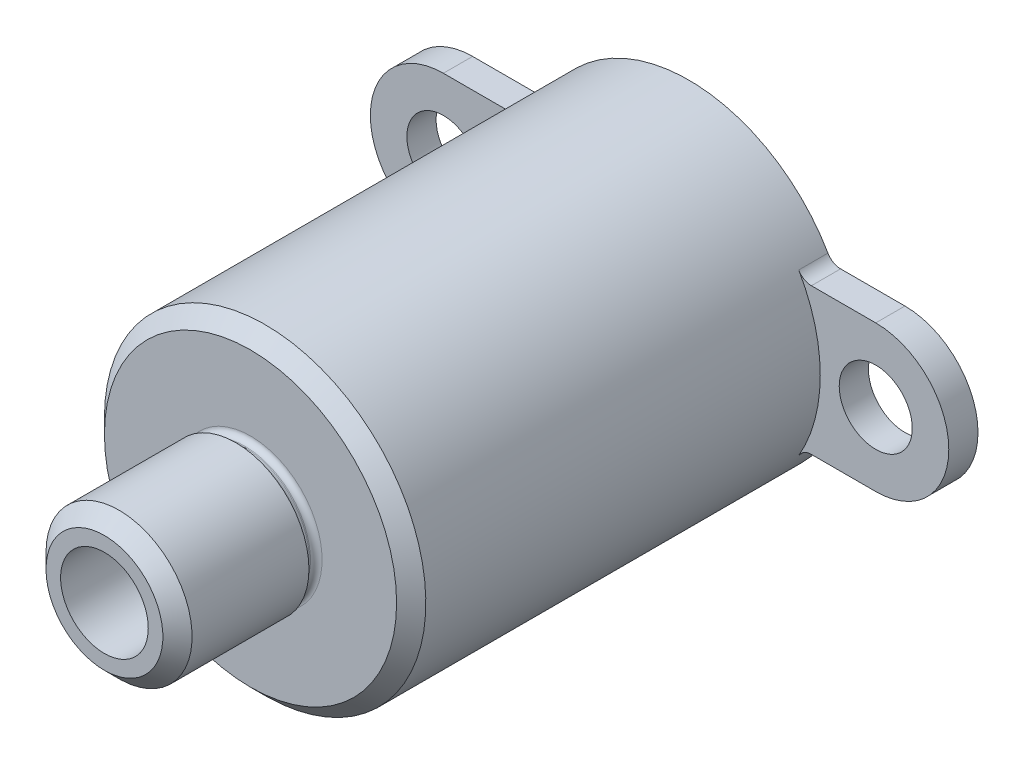
SolidWorks part; units mm, degrees
ref_plane "Спереди" through (0, 0, 0) normal (0, 0, 1) x (1, 0, 0)
ref_plane "Сверху" through (0, 0, 0) normal (0, 1, 0) x (1, 0, 0)
ref_plane "Справа" through (0, 0, 0) normal (1, 0, 0) x (0, 0, -1)
sketch "Эскиз1" plane through (0, 0, 0) normal (1, 0, 0) x (0, 0, -1)
  line L0 (-28.643, 0) -> (42.3762, 0) construction
  line L1 (30, 11) -> (0, 11)
  line L2 (30, 10) -> (25, 10)
  line L3 (30, 11) -> (30, 10)
  line L4 (2, 8) -> (25, 8)
  line L5 (25, 8) -> (25, 10)
  line L6 (-10, 5) -> (0, 5)
  line L7 (-10, 3) -> (2, 3)
  line L8 (0, 11) -> (0, 5)
  line L9 (2, 8) -> (2, 3)
  line L10 (-10, 3) -> (-10, 5)
  dimension "D1" = 30
  dimension "D2" = 22
  dimension "D3" = 20
  dimension "D4" = 2
  dimension "D5" = 5
  dimension "D6" = 10
  dimension "D7" = 6
  dimension "D8" = 10
  dimension "D9" = 2
revolve "Повернуть1" add sketch "Эскиз1" angle 360 about L0
sketch "Эскиз2" plane through (0, 0, 0) normal (0, 1, 0) x (1, 0, 0)
  line L0 (4.5, 0) -> (5, 0)
  line L1 (5, 0) -> (5, -1)
  line L2 (5, -10) -> (5, 0) construction
  line L4 (4.5, -0.7) -> (4.5, 0)
  line L5 (0, 0) -> (0, -7.3244) construction
  line L6 (5, -1) -> (4.5, -0.7)
  dimension "D1" = 0.5
  dimension "D2" = 1
  dimension "D3" = 0.7
revolve "Вырез-Повернуть1" cut sketch "Эскиз2" angle 360 about L5
fillet "Скругление1" radius 0.4 2 edges at (-4.5, 0, 0) (-4.5, 0, 0.7)
sketch "Эскиз3" plane through (0, 0, 0) normal (0, 1, 0) x (1, 0, 0)
  line L0 (0, 0) -> (0, 36.5873) construction
  line L1 (-10, 25) -> (-10.2236, 25)
  line L2 (-10.2236, 25) -> (-10.2236, 25.5)
  line L4 (-10, 25.7) -> (-10, 25)
  line L7 (-10.2236, 25.5) -> (-10, 25.7)
  line L8 (-10, 30) -> (-10, 25) construction
  point P6 (0, 0)
  dimension "D1" = 0.3
  dimension "D2" = 0.5
  dimension "D3" = 0.7
revolve "Вырез-Повернуть2" cut sketch "Эскиз3" angle 360 about L0
fillet "Скругление2" radius 0.2 2 edges at (10.2236, 0, -25.5) (10.2236, 0, -25)
chamfer "Фаска1" distance 1 angle 45 3 edges at (5, 0, 10) (8, 0, -25) (11, 0, 0)
fillet "Скругление3" radius 1 1 edges at (8, 0, -2)
sketch "Эскиз4" plane through (0, 0, -30) normal (0, 0, -1) x (-1, 0, 0)
  line L0 (-22.9294, 0) -> (20.459, 0) construction
  line L1 (-14.798, 5) -> (-9.798, 5)
  line L2 (-14.798, -5) -> (-9.798, -5)
  arc A0 (-9.798, 5) -> (-9.798, -5) centre (0, 0) ccw
  circle A1 centre (0, 0) radius 11 construction
  arc A2 (-14.798, 5) -> (-14.798, -5) centre (-14.798, 0) ccw
  dimension "D1" = 5
  dimension "D2" = 5
extrude "Бобышка-Вытянуть1" add sketch "Эскиз4" against normal blind 2
hole_wizard "Диаметр отверстия Ø5.0 (5)1" positions "Эскиз5" profile "Эскиз6" hole size "Ø5.0" standard "Ansi Metric" end condition through all
sketch "Эскиз5" plane through (0, 0, -30) normal (0, 0, -1) x (-1, 0, 0)
  point P0 (-14.798, 0)
sketch "Эскиз6" plane through (14.798, 0, -30) normal (1, 0, 0) x (0, 1, 0)
  line L0 (0, 0) -> (0, 40)
  line L1 (0, 40) -> (2.5, 40)
  line L2 (2.5, 40) -> (2.5, 0)
  line L5 (2.5, 0) -> (0, 0)
  line L11 (0, -6.35) -> (0, 107.95) construction
  dimension "Диаметр сквозного отверстия" = 5
  dimension "Глубина сквозного отверстия" = 40
mirror "Зеркальное отражение1" about plane through (0, 0, 0) normal (1, 0, 0) of "Бобышка-Вытянуть1", "Диаметр отверстия Ø5.0 (5)1"
chamfer "Фаска2" distance 0.5 angle 45 1 edges at (10, 0, -30)
fillet "Скругление4" radius 1 4 edges at (-9.798, -5, -29) (-9.798, 5, -29) (9.798, -5, -29) (9.798, 5, -29)
